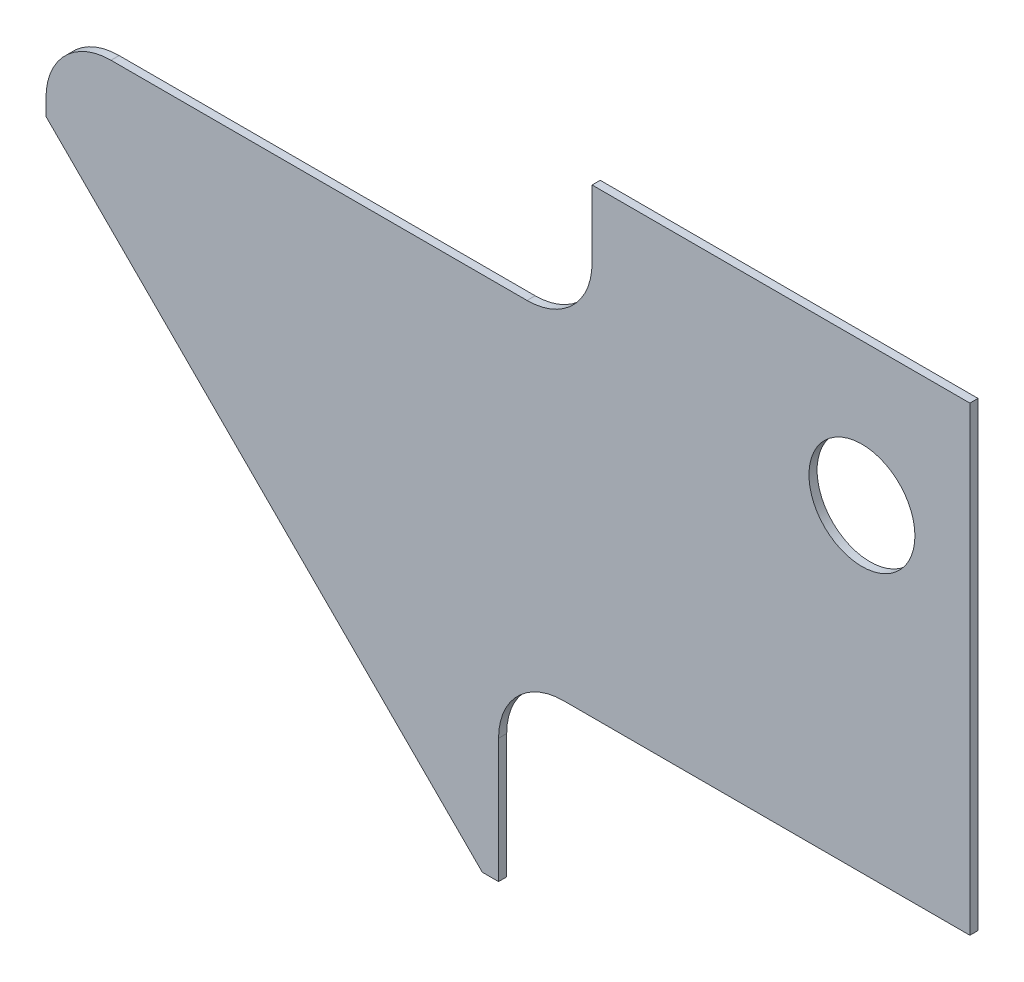
SolidWorks part; units mm, degrees
ref_plane "Front Plane" through (0, 0, 0) normal (0, 0, 1) x (1, 0, 0)
ref_plane "Top Plane" through (0, 0, 0) normal (0, 1, 0) x (1, 0, 0)
ref_plane "Right Plane" through (0, 0, 0) normal (1, 0, 0) x (0, 0, -1)
sketch "Sketch1" plane through (0, 0, 0) normal (0, 0, 1) x (1, 0, 0)
  line L0 (-138.2594, 48.9915) -> (32.2106, -121.4785)
  line L1 (32.2106, -121.4785) -> (222.7106, -121.4785)
  line L2 (-138.2594, 145.2215) -> (-138.2594, 48.9915)
  line L3 (-138.2594, 145.2215) -> (222.7106, 145.2215)
  line L4 (222.7106, -121.4785) -> (222.7106, 145.2215)
  circle A0 centre (180.538, 76.832) radius 20.701
  circle A2 centre (180.538, 76.832) radius 64.9605 construction
  circle A3 centre (180.538, 76.832) radius 318.7974 construction
  point P0 (0, 0)
  point P2 (180.538, 76.832)
  dimension "D4" = 198.3105
  dimension "D1" = 45
  dimension "D2" = 266.7
  dimension "D5" = 245.11
extrude "Boss-Extrude1" add sketch "Sketch1" along normal blind 3.175
sketch "Sketch2" plane through (0, 0, 3.175) normal (0, 0, 1) x (1, 0, 0)
  line L0 (32.2106, -121.4785) -> (222.7106, -121.4785) construction
  line L1 (222.7634, -121.4785) -> (38.5606, -121.4785)
  line L2 (222.7634, -121.4785) -> (222.7634, -47.5645)
  line L3 (222.7634, -47.5645) -> (38.5606, -47.5645)
  line L4 (38.5606, -121.4785) -> (38.5606, -47.5645)
extrude "Cut-Extrude1" cut sketch "Sketch2" against normal through all contours L3 L4 L1 L2
fillet "Fillet1" radius 25.4 1 edges at (38.5606, -47.5645, 1.5875)
sketch "Sketch4" plane through (0, 0, 3.175) normal (0, 0, 1) x (1, 0, 0)
  line L1 (-138.2594, 145.2215) -> (-138.2594, 48.9915) construction
  line L3 (-138.2594, 145.2215) -> (75.1006, 145.2215)
  line L4 (-138.2594, 145.2215) -> (-138.2594, 80.7415)
  line L5 (-138.2594, 80.7415) -> (75.1006, 80.7415)
  line L6 (75.1006, 145.2215) -> (75.1006, 80.7415)
extrude "Cut-Extrude2" cut sketch "Sketch4" against normal through all contours L5 L6 L3 L4
fillet "Fillet2" radius 25.4 2 edges at (-138.2594, 80.7415, 1.5875) (75.1006, 80.7415, 1.5875)
sketch "Sketch7" plane through (0, 0, 3.175) normal (0, 0, 1) x (1, 0, 0)
  line L0 (222.7106, -47.5645) -> (222.7106, 145.2215) construction
  line L1 (75.1006, 145.2215) -> (222.7106, 145.2215)
  line L2 (75.1006, 145.2215) -> (75.1006, 132.5215)
  line L3 (75.1006, 132.5215) -> (222.7106, 132.5215)
  line L4 (222.7106, 145.2215) -> (222.7106, 132.5215)
  dimension "D1" = 12.7
extrude "Cut-Extrude4" cut sketch "Sketch7" against normal through all
